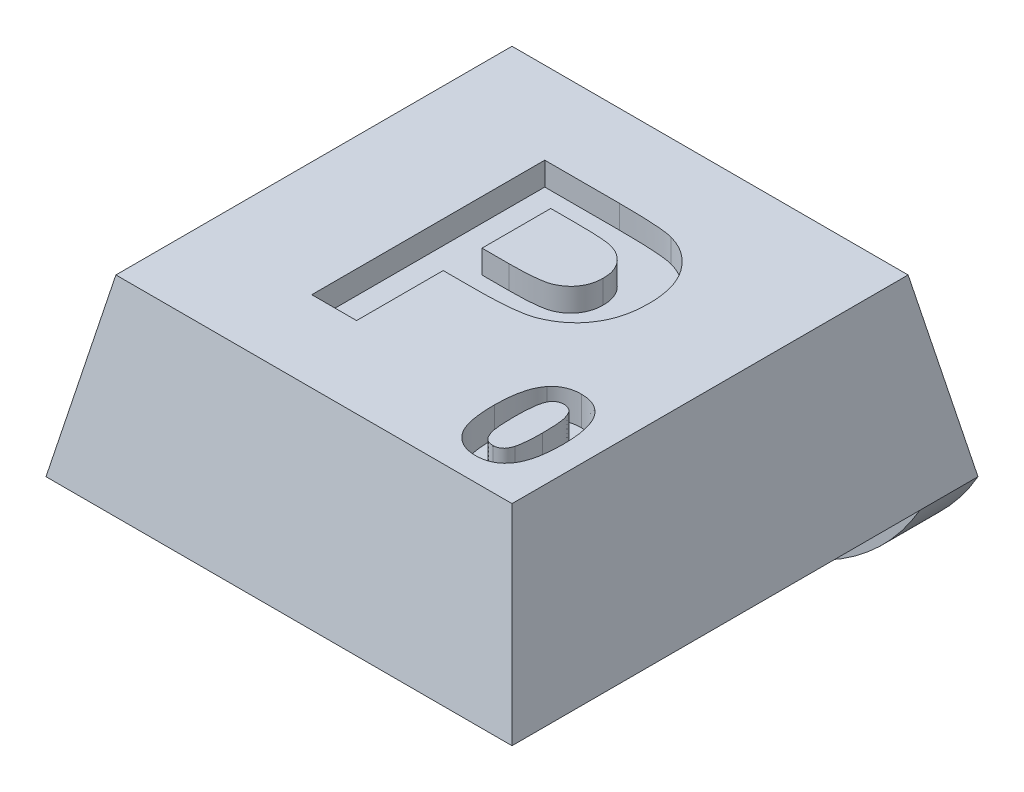
SolidWorks part; units mm, degrees
ref_plane "Front Plane" through (0, 0, 0) normal (0, 0, 1) x (1, 0, 0)
ref_plane "Top Plane" through (0, 0, 0) normal (0, 1, 0) x (1, 0, 0)
ref_plane "Right Plane" through (0, 0, 0) normal (1, 0, 0) x (0, 0, -1)
sketch "Sketch1" plane through (0, 0, 0) normal (0, 1, 0) x (1, 0, 0)
  line L1 (0, 0) -> (8, 0)
  line L2 (0, 0) -> (0, 8)
  line L3 (0, 8) -> (8, 8)
  line L4 (8, 0) -> (8, 8)
  dimension "D1" = 8
  dimension "D2" = 8
extrude "Boss-Extrude1" add sketch "Sketch1" along normal blind 3
sketch "Sketch2" plane through (0, 0, 0) normal (0, 0, 1) x (1, 0, 0)
  line L0 (0, 0) -> (0.6, 3)
  line L1 (0, 3) -> (8, 3) construction
  line L2 (0.6, 3) -> (0, 3)
  line L3 (0, 3) -> (0, 0)
  line L4 (8, 0) -> (7.4, 3)
  line L5 (7.4, 3) -> (8, 3)
  line L6 (8, 3) -> (8, 0)
  dimension "D1" = 0.6
  dimension "D2" = 0.6
extrude "Cut-Extrude1" cut sketch "Sketch2" against normal through all both and the other way through all
sketch "Sketch3" plane through (0, 0, 0) normal (1, 0, 0) x (0, 0, -1)
  line L0 (0, 0) -> (0.6, 3)
  line L1 (8, 3) -> (0, 3) construction
  line L2 (0.6, 3) -> (0, 3)
  line L3 (0, 3) -> (0, 0)
  line L4 (8, 3) -> (7.4, 3)
  line L5 (7.4, 3) -> (8, 0)
  line L6 (8, 3) -> (8, 0)
  dimension "D1" = 0.6
  dimension "D2" = 0.6
extrude "Cut-Extrude2" cut sketch "Sketch3" along normal blind 11
sketch "Sketch4" plane through (0, 0, 0) normal (0, -1, 0) x (1, 0, 0)
  line L0 (8, 0) -> (8, -8) construction
  line L3 (0, 0) -> (8, 0) construction
  circle A0 centre (4, -3.75) radius 1.75
  dimension "D1" = 3.5
  dimension "D2" = 4
  dimension "D3" = 3.75
extrude "Cut-Extrude3" cut sketch "Sketch4" against normal blind 0.4
sketch "Sketch5" plane through (0, 0, 0) normal (0, -1, 0) x (1, 0, 0)
  line L0 (8, 0) -> (8, -8) construction
  line L1 (0, -8) -> (8, -8)
  line L2 (0, -8) -> (0, -7)
  line L3 (0, -7) -> (8, -7)
  line L4 (8, -8) -> (8, -7)
  dimension "D1" = 1
extrude "Boss-Extrude2" add sketch "Sketch5" along normal blind 2
fillet "Fillet1" radius 4 2 edges at (8, -2, -7.5) (0, -2, -7.5)
sketch "Sketch6" plane through (0, 3, 0) normal (0, 1, 0) x (1, 0, 0)
  text T0 "P" font "Arial" height 4
extrude "Cut-Extrude4" cut sketch "Sketch6" against normal blind 0.4
sketch "Sketch7" plane through (0, 3, 0) normal (0, 1, 0) x (1, 0, 0)
  text T0 "0" font "Arial" height 1.8
extrude "Cut-Extrude5" cut sketch "Sketch7" against normal blind 0.5
